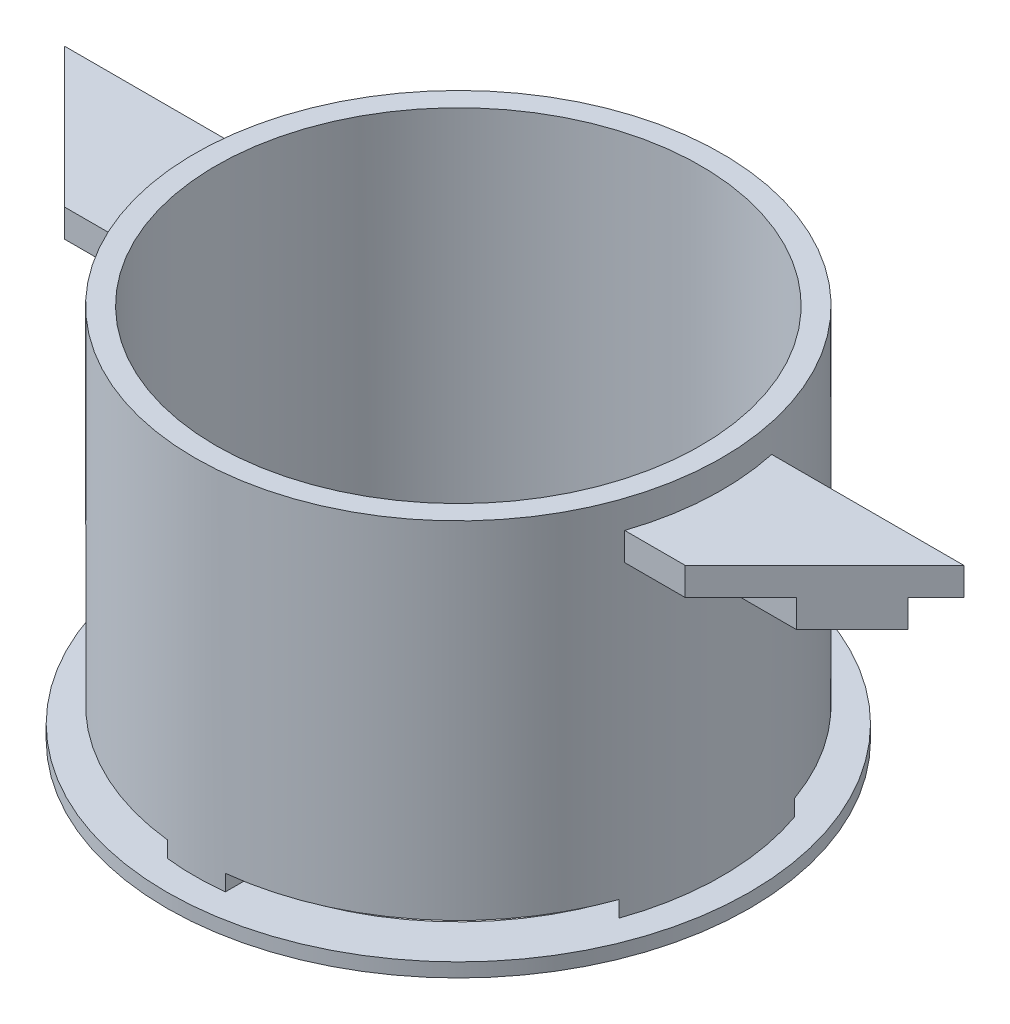
SolidWorks part; units mm, degrees
ref_plane "Front Plane" through (0, 0, 0) normal (0, 0, 1) x (1, 0, 0)
ref_plane "Top Plane" through (0, 0, 0) normal (0, 1, 0) x (1, 0, 0)
ref_plane "Right Plane" through (0, 0, 0) normal (1, 0, 0) x (0, 0, -1)
sketch "Sketch1" plane through (0, 0, 0) normal (0, 1, 0) x (1, 0, 0)
  circle A0 centre (0, 0) radius 60.071
  dimension "D2" = 120.142
extrude "Boss-Extrude1" add sketch "Sketch1" along normal blind 88.9
sketch "Sketch2" plane through (0, 88.9, 0) normal (0, 1, 0) x (1, 0, 0)
  circle A0 centre (0, 0) radius 55.245
  dimension "D1" = 110.49
extrude "Cut-Extrude1" cut sketch "Sketch2" against normal through all
sketch "Sketch6" plane through (0, 0, 0) normal (0, 0, 1) x (1, 0, 0)
  line L0 (-60.071, 88.9) -> (-60.071, 0) construction
  line L1 (-56.642, 10.033) -> (-6.604, 10.033)
  line L2 (-56.642, 10.033) -> (-56.642, 6.35)
  line L3 (-56.642, 6.35) -> (-6.604, 6.35)
  line L7 (-55.245, 0) -> (55.245, 0) construction
  line L8 (-6.604, 10.033) -> (-6.604, 6.35)
  line L9 (0, 0) -> (0, 21.9448) construction
  line L10 (6.604, 10.033) -> (6.604, 6.35)
  line L11 (56.642, 6.35) -> (6.604, 6.35)
  line L12 (56.642, 10.033) -> (6.604, 10.033)
  line L13 (56.642, 10.033) -> (56.642, 6.35)
  dimension "D2" = 3.429
  dimension "D3" = 3.683
  dimension "D4" = 6.35
  dimension "D1" = 6.604
extrude "Cut-Extrude4" cut sketch "Sketch6" against normal through all both and the other way through all
ref_plane "Plane1" through (0, 69.85, 0) normal (0, 1, 0) x (1, 0, 0)
sketch "Sketch10" plane through (0, 0, 0) normal (0, 1, 0) x (1, 0, 0)
  circle A0 centre (0, 0) radius 63.5
  circle A1 centre (0, 0) radius 60.071 construction
  circle A2 centre (0, 0) radius 60.071
  dimension "D1" = 127
sketch "Sketch9" plane through (0, 69.85, 0) normal (0, 1, 0) x (1, 0, 0)
  line L1 (-83.4526, -6.35) -> (-54.8788, -6.35)
  line L3 (-96.1526, 6.35) -> (-54.8788, 6.35)
  line L7 (-96.1526, 6.35) -> (-83.4526, -6.35)
  circle A0 centre (0, 0) radius 55.245 construction
  arc A1 (-54.8788, 6.35) -> (-54.8788, -6.35) centre (0, 0) ccw
  point P0 (0, 0)
  point P2 (-89.8026, 0)
  dimension "D1" = 96.1526
  dimension "D2" = 45
  dimension "D4" = 12.7
extrude "Boss-Extrude6" add sketch "Sketch9" along normal blind 12.7
sketch "Sketch11" plane through (0, 82.55, 0) normal (0, 1, 0) x (1, 0, 0)
  line L0 (-70.7526, -19.05) -> (-70.7526, 12.7) construction
  line L1 (-70.7526, 12.7) -> (-102.5026, 12.7)
  line L2 (-102.5026, 12.7) -> (-70.7526, -19.05)
  line L3 (-96.1526, 6.35) -> (-83.4526, -6.35) construction
  line L4 (-59.7344, 6.35) -> (-96.1526, 6.35) construction
  line L5 (-83.4526, -6.35) -> (-59.7344, -6.35) construction
  line L6 (-70.7526, -19.05) -> (-56.9704, -19.05)
  line L7 (-56.9704, -19.05) -> (-56.9704, 12.7)
  line L8 (-56.9704, 12.7) -> (-70.7526, 12.7)
  circle A1 centre (0, 0) radius 60.071 construction
  dimension "D1" = 6.35
  dimension "D2" = 12.7
extrude "Boss-Extrude8" add sketch "Sketch11" against normal blind 6.35
mirror "Mirror1" about plane through (0, 0, 0) normal (1, 0, 0) of "Boss-Extrude6", "Boss-Extrude8"
sketch "Sketch12" plane through (0, 0, 0) normal (0, -1, 0) x (1, 0, 0)
  circle A0 centre (0, 0) radius 60.071 construction
  circle A1 centre (0, 0) radius 60.071
  circle A2 centre (0, 0) radius 66.421
  dimension "D1" = 6.35
extrude "Boss-Extrude9" add sketch "Sketch12" along normal blind 3.175 from surface starting at face at (-33.2949, 6.35, 0)
equation "\"tightTol\" = 0.005in"
equation "\"normTol\"= 0.01in"
equation "\"looseTol\"= 0.02in"
equation "\"D2@Sketch6\"=\"normTol\"+0.125000in"
equation "\"D1@Sketch6\"=\"normTol\"+0.250000in"
equation "\"D3@Sketch6\"=\"looseTol\"+0.125000in"
equation "\"D2@Sketch1\"=4.750000in-\"looseTol\""
